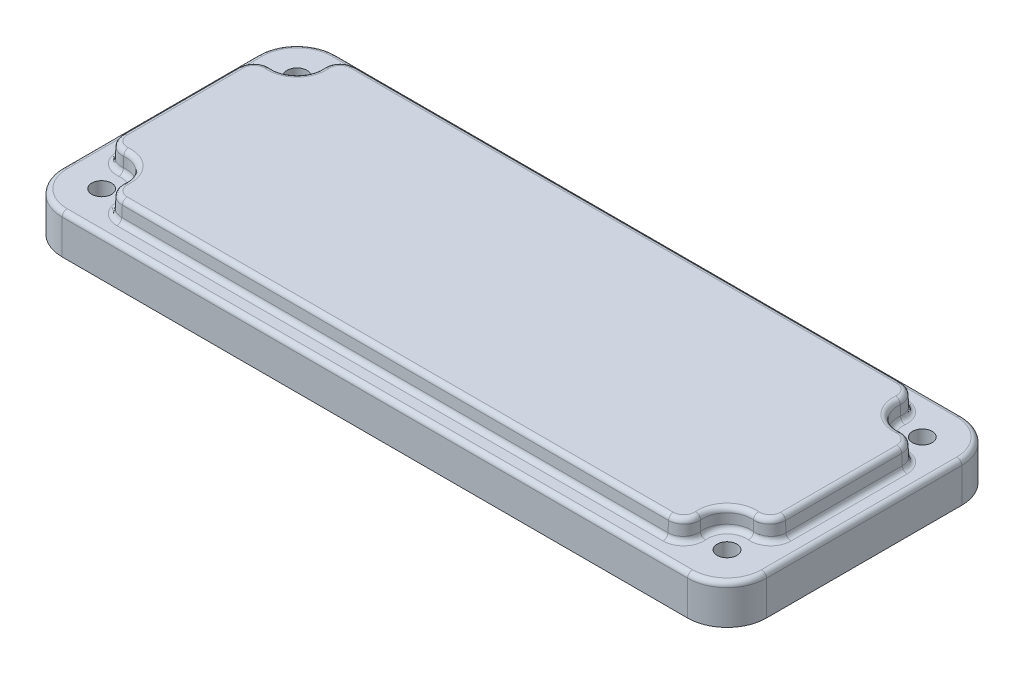
SolidWorks part; units mm, degrees
material "PW20:29:Sc:0:"
ref_plane "Front" through (0, 0, 0) normal (0, 0, 1) x (1, 0, 0)
ref_plane "Top" through (0, 0, 0) normal (0, 1, 0) x (1, 0, 0)
ref_plane "Right" through (0, 0, 0) normal (1, 0, 0) x (0, 0, -1)
sketch "Sketch1" plane through (0, 0, 0) normal (0, 1, 0) x (1, 0, 0)
  line L0 (-50.75, 22.25) -> (50.75, 22.25)
  line L1 (-57.15, 15.85) -> (-57.15, -15.85)
  line L2 (50.75, -22.25) -> (-50.75, -22.25)
  line L3 (57.15, -15.85) -> (57.15, 15.85)
  line L4 (-50.75, -15.85) -> (50.75, 15.85) construction
  arc A0 (-57.15, -15.85) -> (-50.75, -22.25) centre (-50.75, -15.85) ccw
  arc A1 (57.15, -15.85) -> (50.75, -22.25) centre (50.75, -15.85) cw
  arc A2 (50.75, 22.25) -> (57.15, 15.85) centre (50.75, 15.85) cw
  arc A3 (-50.75, 22.25) -> (-57.15, 15.85) centre (-50.75, 15.85) ccw
  dimension "D1" = 114.3
  dimension "D2" = 44.5
  dimension "D4" = 6.4
extrude "Base-Extrude" add sketch "Sketch1" along normal blind 6.4
sketch "Sketch2" plane through (0, 6.4, 0) normal (0, 1, 0) x (-1, 0, 0)
  line L4 (50.75, 19.05) -> (-50.75, 19.05)
  line L5 (-53.95, 15.85) -> (-53.95, -15.85)
  line L6 (-50.75, -19.05) -> (50.75, -19.05)
  line L7 (53.95, -15.85) -> (53.95, 15.85)
  line L8 (50.75, 19.05) -> (-50.75, 19.05)
  line L9 (-53.95, 15.85) -> (-53.95, -15.85)
  line L10 (-50.75, -19.05) -> (50.75, -19.05)
  line L11 (53.95, -15.85) -> (53.95, 15.85)
  arc A4 (53.95, 15.85) -> (50.75, 19.05) centre (50.75, 15.85) ccw
  arc A5 (53.95, 15.85) -> (50.75, 19.05) centre (50.75, 15.85) ccw
  arc A6 (-50.75, 19.05) -> (-53.95, 15.85) centre (-50.75, 15.85) ccw
  arc A7 (-50.75, 19.05) -> (-53.95, 15.85) centre (-50.75, 15.85) ccw
  arc A8 (-53.95, -15.85) -> (-50.75, -19.05) centre (-50.75, -15.85) ccw
  arc A9 (-53.95, -15.85) -> (-50.75, -19.05) centre (-50.75, -15.85) ccw
  arc A10 (50.75, -19.05) -> (53.95, -15.85) centre (50.75, -15.85) ccw
  arc A11 (50.75, -19.05) -> (53.95, -15.85) centre (50.75, -15.85) ccw
  dimension "D1" = 3.2
extrude "Boss-Extrude1" add sketch "Sketch2" along normal blind 3.2 draft 3
sketch "Sketch3" plane through (0, 9.6, 0) normal (0, 1, 0) x (-1, 0, 0)
  circle A0 centre (-50.75, 15.85) radius 3.95
  dimension "D1" = 7.9
extrude "Cut-Extrude1" cut sketch "Sketch3" against normal up to surface (3.2 mm away)
sketch "Sketch4" plane through (0, 6.4, 0) normal (0, 1, 0) x (-1, 0, 0)
  circle A0 centre (-50.75, 15.85) radius 1.6
  dimension "D1" = 3.2
extrude "Cut-Extrude2" cut sketch "Sketch4" against normal through all
mirror "Mirror1" about plane through (0, 0, 0) normal (0, 0, 1) of "Cut-Extrude2", "Cut-Extrude1"
mirror "Mirror2" about plane through (0, 0, 0) normal (1, 0, 0) of "Mirror1"
fillet "Fillet1" radius 2.5 8 edges at (48.325, 7.9644, 18.968) (53.868, 7.9644, 13.425) (53.868, 7.9644, -13.425) (48.325, 7.9644, -18.968) (-48.325, 7.9644, -18.968) (-53.868, 7.9644, -13.425) (-53.868, 7.9644, 13.425) (-48.325, 7.9644, 18.968)
fillet "Fillet2" radius 0.8 40 edges at (0, 6.4, -19.05) (0, 9.6, -18.8823) (-46.2654, 6.4, -18.1412) (46.1315, 6.4, -18.2909) (-45.8822, 9.6, -18.3351) (46.3944, 9.6, -17.7792) (-47.9569, 6.4, -13.0569) (47.9569, 6.4, -13.0569) (-47.9569, 9.6, -13.0569) (47.9569, 9.6, -13.0569) (-53.2081, 6.4, -11.2146) (53.0328, 6.4, -11.3723) (-52.6792, 9.6, -11.4944) (53.2351, 9.6, -10.9822) (0, 6.4, -22.25) (-53.95, 6.4, 0) (53.95, 6.4, 0) (-53.7823, 9.6, 0) (53.7823, 9.6, 0) (55.2755, 6.4, -20.3755) (-55.2755, 6.4, -20.3755) (-53.0065, 6.4, 11.3935) (53.2274, 6.4, 11.1954) (-53.2351, 9.6, 10.9822) (52.6792, 9.6, 11.4944) (57.15, 6.4, 0) (-57.15, 6.4, 0) (-47.9569, 6.4, 13.0569) (47.9569, 6.4, 13.0569) (-47.9569, 9.6, 13.0569) (47.9569, 9.6, 13.0569) (55.2755, 6.4, 20.3755) (-55.2755, 6.4, 20.3755) (-46.0943, 6.4, 18.3284) (46.294, 6.4, 18.106) (-46.3944, 9.6, 17.7792) (45.8822, 9.6, 18.3351) (0, 6.4, 22.25) (0, 6.4, 19.05) (0, 9.6, 18.8823)
sketch "Sketch5" plane through (0, 0, 0) normal (0, -1, 0) x (1, 0, 0)
  line L0 (-44.45, 15.85) -> (44.45, 15.85)
  line L1 (-44.45, 15.85) -> (-44.45, -15.85)
  line L2 (44.45, -15.85) -> (-44.45, -15.85)
  line L3 (44.45, -15.85) -> (44.45, 15.85)
  line L4 (50.75, 22.25) -> (-50.75, 22.25) construction
  line L5 (57.15, 15.85) -> (57.15, -15.85) construction
  line L6 (-57.15, -15.85) -> (-57.15, 15.85) construction
  line L7 (-50.75, -22.25) -> (50.75, -22.25) construction
  dimension "D1" = 6.4
  dimension "D2" = 12.7
  dimension "D3" = 12.7
  dimension "D4" = 6.4
extrude "Cut-Extrude3" cut sketch "Sketch5" against normal blind 6.4 draft 3
fillet "Fillet3" radius 6.4 4 edges at (44.2823, 3.2, 15.6823) (44.2823, 3.2, -15.6823) (-44.2823, 3.2, 15.6823) (-44.2823, 3.2, -15.6823)
fillet "Fillet4" radius 3.2 8 edges at (44.1146, 6.4, 0) (42.2437, 6.4, 13.6437) (42.2437, 6.4, -13.6437) (0, 6.4, 15.5146) (0, 6.4, -15.5146) (-42.2437, 6.4, 13.6437) (-42.2437, 6.4, -13.6437) (-44.1146, 6.4, 0)
